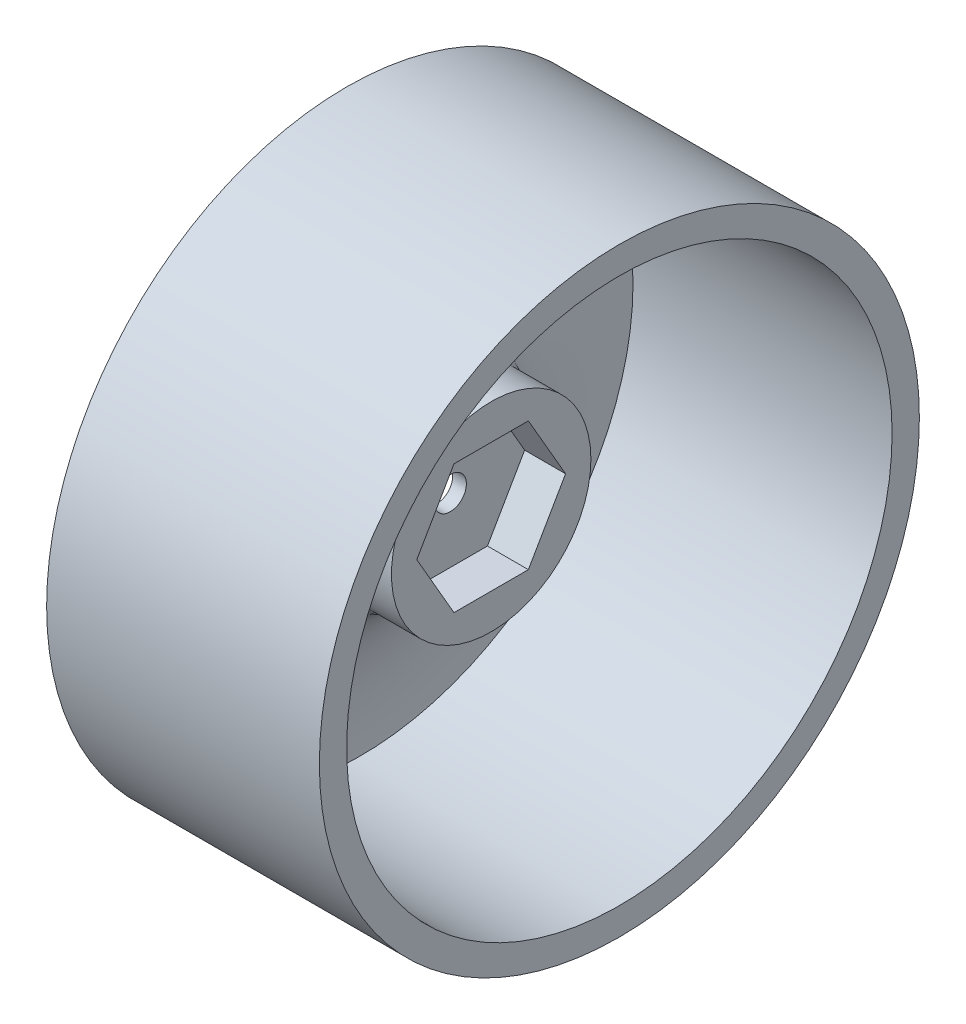
SolidWorks part; units mm, degrees
ref_plane "Front Plane" through (0, 0, 0) normal (0, 0, 1) x (1, 0, 0)
ref_plane "Top Plane" through (0, 0, 0) normal (0, 1, 0) x (1, 0, 0)
ref_plane "Right Plane" through (0, 0, 0) normal (1, 0, 0) x (0, 0, -1)
sketch "Reference" plane through (0, 0, 0) normal (0, 1, 0) x (1, 0, 0)
  line L0 (0, 25.4) -> (0, 0) construction
  line L5 (-12.7, -27.94) -> (12.7, -27.94) construction
  line L6 (-12.7, -27.94) -> (-12.7, 27.94) construction
  line L7 (-12.7, 27.94) -> (12.7, 27.94) construction
  line L8 (12.7, 25.4) -> (12.7, 27.94) construction
  line L9 (-12.7, -27.94) -> (12.7, 27.94) construction
  line L10 (-12.7, 27.94) -> (12.7, -27.94) construction
  line L11 (-12.7, 27.94) -> (12.7, 27.94) construction
  line L12 (-12.7, 25.4) -> (12.7, 25.4) construction
  line L13 (-3.81, 8.0187) -> (-3.81, 0) construction
  line L14 (-3.81, 8.0187) -> (0.762, 8.0187) construction
  line L15 (-12.7, 25.4) -> (12.7, 25.4) construction
  line L16 (-3.81, 9.2887) -> (0.762, 9.2887) construction
  line L17 (-4.318, 8.128) -> (-4.318, 0) construction
  spline S0 degree 2 poles (-12.7, 25.4) (-12.5305, 5.9834) (0.762, 8.0187) knots 0 0 0 1 1 1 construction
  spline S1 degree 2 poles (-3.81, 9.2887) (-11.4848, 10.4752) (-11.43, 25.4) knots 0 0 0 1 1 1 construction
  point P0 (0, 0)
  point P15 (-3.81, 4.0093)
  point P18 (0, 0)
  point P21 (0.6293, 7.27)
  point P22 (-4.318, 7.27)
  point P23 (1.0079, 7.27)
  point P24 (0, 0)
  point P25 (0, 0)
  point P26 (0, 0)
  point P27 (1.0694, 7.27)
  point P28 (-3.81, -2.255)
  point P29 (0, 0)
  point P30 (0, 0)
  point P31 (0, 0)
  point P32 (-3.81, -3.4105)
  point P33 (0, 0)
  point P34 (-3.81, -0.237)
  point P35 (0, 0)
  dimension "D8" = 0.508
  dimension "D1" = 25.4
  dimension "D2" = 55.88
  dimension "D3" = 2.54
  dimension "D4" = 8.128
  dimension "D5" = 4.572
  dimension "D6" = 1.27
  dimension "D7" = 1.27
  dimension "D9" = 0.762
sketch "Sketch2" plane through (0, 0, 0) normal (0, 1, 0) x (1, 0, 0)
  line L3 (0.762, 8.0187) -> (0.762, 9.2887)
  line L4 (0.762, 9.2887) -> (-3.81, 9.2887)
  line L5 (-4.318, 8.128) -> (-4.318, 0)
  line L7 (-12.7, 25.4) -> (-12.7, 27.94)
  line L8 (-12.7, 27.94) -> (12.7, 27.94)
  line L9 (12.7, 27.94) -> (12.7, 25.4)
  line L11 (-11.43, 25.4) -> (12.7, 25.4)
  line L12 (0.762, 8.0187) -> (0.762, 0)
  line L13 (0.762, 0) -> (-4.318, 0)
  spline S0 degree 2 poles (-4.318, 8.128) (-12.8591, 7.3367) (-12.7, 25.4) knots 0 0 0 1 1 1
  spline S1 degree 3 poles (-11.43, 25.4) (-11.6399, 16.186) (-9.5776, 10.5416) (-3.81, 9.2887) knots 0 0 0 0 1 1 1 1
revolve "Main Revolve" add sketch "Sketch2" angle 360 about L13
sketch "Sketch5" plane through (0.762, 0, 0) normal (1, 0, 0) x (0, 0, -1)
  line L1 (6.9282, 0) -> (3.4641, 6)
  line L2 (3.4641, 6) -> (-3.4641, 6)
  line L3 (-3.4641, 6) -> (-6.9282, 0)
  line L4 (-6.9282, 0) -> (-3.4641, -6)
  line L5 (-3.4641, -6) -> (3.4641, -6)
  line L6 (3.4641, -6) -> (6.9282, 0)
  circle A0 centre (0, 0) radius 6 construction
  dimension "D1" = 12
extrude "Cut-Extrude1" cut sketch "Sketch5" against normal blind 3.81
sketch "Sketch6" plane through (-4.318, 0, 0) normal (-1, 0, 0) x (0, 0, 1)
  circle A0 centre (0, 0) radius 1.5
  dimension "D1" = 3
extrude "Cut-Extrude2" cut sketch "Sketch6" against normal through all
